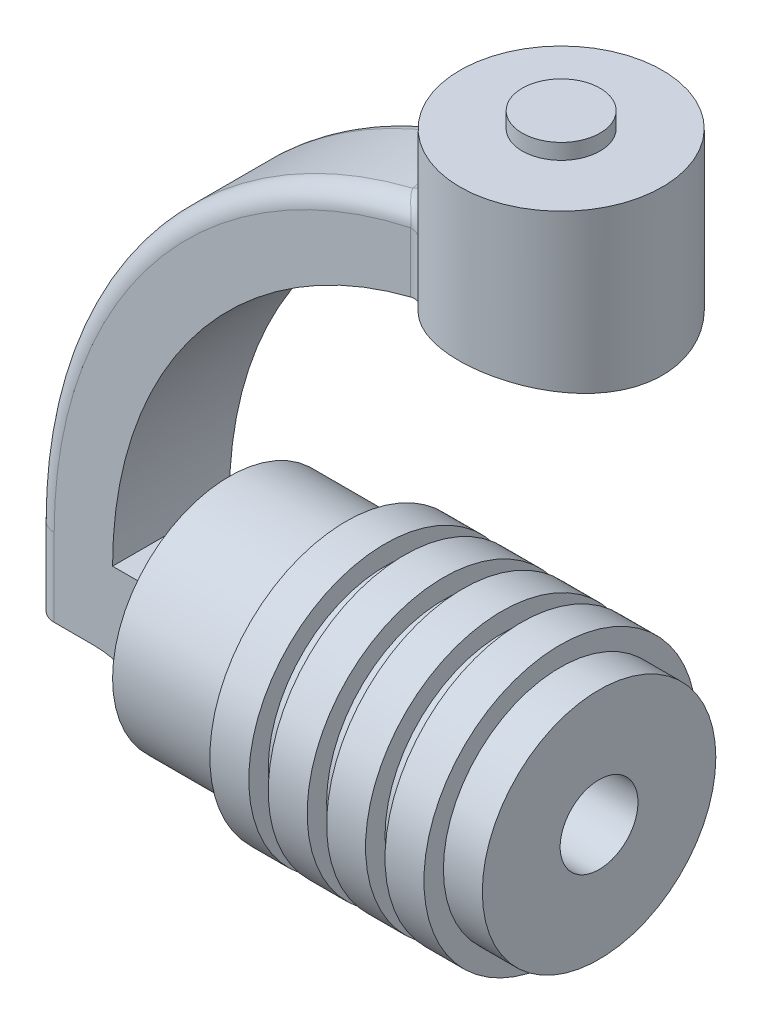
SolidWorks part; units mm, degrees
ref_plane "Ön Düzlem" through (0, 0, 0) normal (0, 0, 1) x (1, 0, 0)
ref_plane "Üst Düzlem" through (0, 0, 0) normal (0, 1, 0) x (1, 0, 0)
ref_plane "Sağ Düzlem" through (0, 0, 0) normal (1, 0, 0) x (0, 0, -1)
sketch "Sketch1" plane through (0, 0, 0) normal (0, 0, 1) x (1, 0, 0)
  line L0 (-110, 0) -> (0, 0) construction
  line L1 (0, 0) -> (0, 190) construction
  line L2 (-110, -20) -> (-90, -20)
  line L3 (-90, -20) -> (-90, -40)
  line L4 (-90, -40) -> (-130, -40)
  line L5 (-130, -40) -> (-130, 0)
  line L6 (-110, -20) -> (-110, 0)
  line L7 (-130, 0) -> (-130, 70)
  line L8 (-110, 0) -> (-110, 70)
  line L9 (-130, 0) -> (-110, 0) construction
  line L10 (-26, 169.7535) -> (-26, 190) construction
  line L11 (-26, 190) -> (0, 190) construction
  line L12 (-26, 169.7535) -> (-29.4043, 189.4617)
  arc A0 (-110, 70) -> (-26, 169.7535) centre (-8.7692, 70) cw
  arc A1 (-130, 70) -> (-29.4043, 189.4617) centre (-8.7692, 70) cw
  arc A2 (-29.4043, 189.4617) -> (-26, 190) centre (-8.7692, 70) cw construction
  dimension "D1" = 40
  dimension "D2" = 20
  dimension "D3" = 20
  dimension "D4" = 110
  dimension "D5" = 40
  dimension "D6" = 190
  dimension "D7" = 26
  dimension "D8" = 20
  dimension "D9" = 70
extrude "Boss-Extrude1" add sketch "Sketch1" along normal blind 30
sketch "Sketch2" plane through (-90, 0, 0) normal (1, 0, 0) x (0, 0, -1)
  line L0 (-30, -30) -> (0, -30) construction
  line L1 (-30, -40) -> (-30, -20) construction
  line L2 (0, -40) -> (0, -20) construction
  circle A0 centre (-15, -30) radius 30
  dimension "D1" = 60
extrude "Boss-Extrude2" add sketch "Sketch2" along normal blind 90 and the other way blind 5
sketch "Sketch3" plane through (0, 0, 0) normal (1, 0, 0) x (0, 0, -1)
  circle A0 centre (-15, -30) radius 35
  dimension "D1" = 70
extrude "Boss-Extrude3" add sketch "Sketch3" against normal blind 10 from offset 10 offset against normal yes
pattern_linear "LPattern1" count 4 spacing 15 along (-1, 0, 0) of "Boss-Extrude3"
sketch "Sketch4" plane through (0, 0, 0) normal (1, 0, 0) x (0, 0, -1)
  circle A0 centre (-15, -30) radius 10
  dimension "D1" = 20
extrude "Cut-Extrude1" cut sketch "Sketch4" against normal blind 20
ref_plane "Plane1" through (0, 0, 0) normal (0, 1, 0) x (1, 0, 0)
ref_plane "Plane2" through (0, 190, 0) normal (0, 1, 0) x (1, 0, 0)
sketch "Sketch5" plane through (0, 190, 0) normal (0, 1, 0) x (1, 0, 0)
  line L0 (-29.4043, -15) -> (9.9257, -15) construction
  line L1 (-29.4043, -30) -> (-29.4043, 0) construction
  circle A0 centre (-9.7393, -15) radius 26
  dimension "D2" = 52
  dimension "D1" = 39.33
extrude "Boss-Extrude4" add sketch "Sketch5" along normal blind 20 and the other way up to surface other way up to face at (-77.1015, 127.5409, 15)
sketch "Sketch6" plane through (0, 210, 0) normal (0, 1, 0) x (1, 0, 0)
  circle A0 centre (-9.7393, -15) radius 10
  dimension "D1" = 20
extrude "Boss-Extrude5" add sketch "Sketch6" along normal blind 4
fillet "Fillet1" radius 20 1 edges at (-95, -40, 15)
fillet "Fillet2" radius 5 8 edges at (-30.976, 178.9723, 0) (-30.976, 178.9723, 30) (-130, -40, 15) (-130, 15, 30) (-130, 15, 0) (-102.0137, 147.475, 0) (-35.7028, 188.201, 13.6229) (-102.0137, 147.475, 30)
sketch "Sketch7" plane through (0, 0, 30) normal (0, 0, 1) x (1, 0, 0)
  line L0 (-125, 70) -> (115.4505, 70)
  line L1 (115.4505, 70) -> (115.4505, -105.1287)
  line L2 (115.4505, -105.1287) -> (-201.3786, -105.1287)
  line L3 (-201.3786, -105.1287) -> (-201.3786, 70)
  line L4 (-201.3786, 70) -> (-125, 70)
extrude "Cut-Extrude2" cut sketch "Sketch7" against normal through all and the other way through all
sketch "Sketch8" plane through (0, 70, 0) normal (0, -1, 0) x (1, 0, 0)
  line L4 (-130, 25) -> (-130, 5)
  line L5 (-125, 0) -> (-110, 0)
  line L6 (-110, 0) -> (-110, 30)
  line L7 (-110, 30) -> (-125, 30)
  line L8 (-130, 25) -> (-130, 5)
  line L9 (-125, 0) -> (-110, 0)
  line L10 (-110, 0) -> (-110, 30)
  line L11 (-110, 30) -> (-125, 30)
  arc A2 (-125, 30) -> (-130, 25) centre (-125, 25) ccw
  arc A3 (-130, 5) -> (-125, 0) centre (-125, 5) ccw
  arc A4 (-125, 30) -> (-130, 25) centre (-125, 25) ccw
  arc A5 (-130, 5) -> (-125, 0) centre (-125, 5) ccw
  dimension "D1" = 0
extrude "Boss-Extrude6" add sketch "Sketch8" along normal blind 20
sketch "Sketch9" plane through (-110, 0, 0) normal (1, 0, 0) x (0, 0, -1)
  line L4 (0, 70) -> (-30, 70)
  line L5 (-30, 70) -> (-30, 50)
  line L6 (-30, 50) -> (0, 50)
  line L7 (0, 50) -> (0, 70)
  line L8 (0, 70) -> (-30, 70)
  line L9 (-30, 70) -> (-30, 50)
  line L10 (-30, 50) -> (0, 50)
  line L11 (0, 50) -> (0, 70)
  dimension "D1" = 0
extrude "Boss-Extrude7" add sketch "Sketch9" along normal blind 20
sketch "Sketch10" plane through (-90, 0, 0) normal (1, 0, 0) x (0, 0, -1)
  line L0 (-30, 60) -> (0, 60) construction
  line L1 (-30, 70) -> (-30, 50) construction
  line L2 (0, 50) -> (0, 70) construction
  circle A0 centre (-15, 60) radius 30
  dimension "D1" = 60
extrude "Boss-Extrude8" add sketch "Sketch10" along normal blind 90 and the other way blind 5
sketch "Sketch11" plane through (0, 0, 0) normal (1, 0, 0) x (0, 0, -1)
  circle A0 centre (-15, 60) radius 35
  dimension "D1" = 70
extrude "Boss-Extrude9" add sketch "Sketch11" against normal blind 10 from offset 10 offset against normal yes
pattern_linear "LPattern2" count 4 spacing 15 along (-1, 0, 0) of "Boss-Extrude9"
sketch "Sketch12" plane through (0, 0, 0) normal (1, 0, 0) x (0, 0, -1)
  circle A0 centre (-15, 60) radius 10
  dimension "D1" = 20
extrude "Cut-Extrude3" cut sketch "Sketch12" against normal blind 20
fillet "Fillet3" radius 20 1 edges at (-95, 50, 15)
